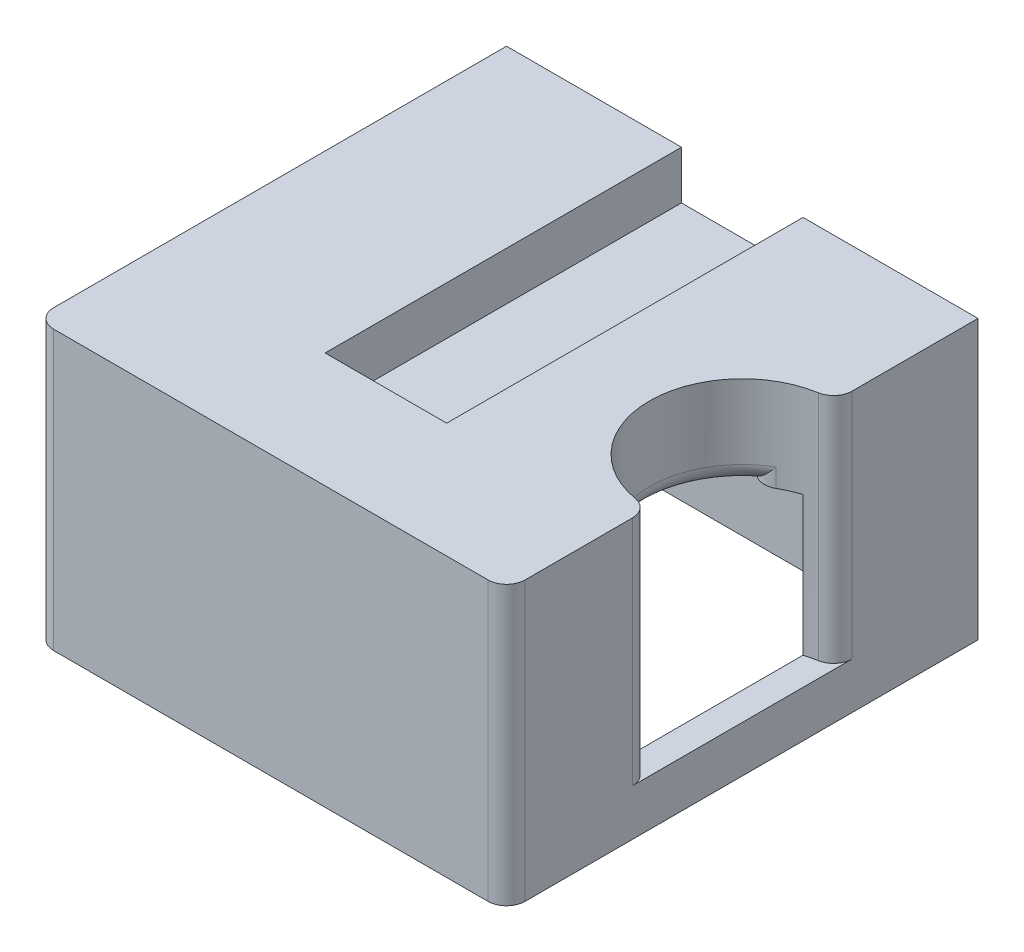
SolidWorks part; units mm, degrees
ref_plane "Front Plane" through (0, 0, 0) normal (0, 0, 1) x (1, 0, 0)
ref_plane "Top Plane" through (0, 0, 0) normal (0, 1, 0) x (1, 0, 0)
ref_plane "Right Plane" through (0, 0, 0) normal (1, 0, 0) x (0, 0, -1)
sketch "Sketch1" plane through (0, 0, 0) normal (0, 1, 0) x (1, 0, 0)
  line L1 (12.7, -12.7) -> (-12.7, -12.7)
  line L2 (12.7, -12.7) -> (12.7, 12.7)
  line L3 (12.7, 12.7) -> (-12.7, 12.7)
  line L4 (-12.7, -12.7) -> (-12.7, 12.7)
  line L5 (12.7, -12.7) -> (-12.7, 12.7) construction
  line L6 (12.7, 12.7) -> (-12.7, -12.7) construction
  line L7 (8.7, -8.7) -> (-8.7, -8.7)
  line L8 (8.7, -8.7) -> (8.7, 8.7)
  line L9 (8.7, 8.7) -> (-8.7, 8.7)
  line L10 (-8.7, -8.7) -> (-8.7, 8.7)
  line L11 (8.7, -8.7) -> (-8.7, 8.7) construction
  line L12 (8.7, 8.7) -> (-8.7, -8.7) construction
  point P0 (0, 0)
  point P6 (0, 0)
  dimension "D1" = 25.4
  dimension "D2" = 25.4
  dimension "D3" = 4
extrude "Boss-Extrude1" add sketch "Sketch1" along normal blind 10
sketch "Sketch2" plane through (0, 0, 0) normal (0, -1, 0) x (-1, 0, 0)
  line L1 (-11.25, 10.75) -> (11.25, 10.75)
  line L2 (-11.25, 10.75) -> (-11.25, -10.75)
  line L3 (-11.25, -10.75) -> (11.25, -10.75)
  line L4 (11.25, 10.75) -> (11.25, -10.75)
  line L5 (-11.25, 10.75) -> (11.25, -10.75) construction
  line L6 (-11.25, -10.75) -> (11.25, 10.75) construction
  point P0 (0, 0)
  dimension "D1" = 22.5
  dimension "D2" = 21.5
hole_wizard "Tap Drill for M2x0.4 Tap1" positions "Sketch3" profile "Sketch4" hole size "M2x0.4" standard "ANSI Metric" end condition through all
sketch "Sketch3" plane through (0, 0, 0) normal (0, -1, 0) x (-1, 0, 0)
  point P0 (11.25, -10.75)
  point P3 (-11.25, -10.75)
  point P6 (-11.25, 10.75)
  point P9 (11.25, 10.75)
sketch "Sketch4" plane through (-11.25, 0, 10.75) normal (1, 0, 0) x (0, 0, -1)
  line L0 (0, 0) -> (0, 10)
  line L1 (0, 10) -> (0.8, 10)
  line L2 (0.8, 10) -> (0.8, 0)
  line L5 (0.8, 0) -> (0, 0)
  line L11 (0, -6.35) -> (0, 107.95) construction
  dimension "Thru Hole Dia." = 1.6
  dimension "Thru Hole Depth" = 10
sketch "Sketch5" plane through (0, 10, 0) normal (0, 1, 0) x (1, 0, 0)
  line L1 (12.7, -12.7) -> (-12.7, -12.7)
  line L2 (12.7, -12.7) -> (12.7, 12.7)
  line L3 (12.7, 12.7) -> (-12.7, 12.7)
  line L4 (-12.7, -12.7) -> (-12.7, 12.7)
extrude "Boss-Extrude2" add sketch "Sketch5" along normal blind 5
sketch "Sketch6" plane through (0, 15, 0) normal (0, 1, 0) x (1, 0, 0)
  line L0 (11.25, 10.75) -> (-11.25, -10.75) construction
  line L1 (-3.275, -12.7) -> (3.275, -12.7)
  line L2 (-3.275, -12.7) -> (-3.275, 12.7)
  line L3 (-3.275, 12.7) -> (3.275, 12.7)
  line L4 (3.275, -12.7) -> (3.275, 12.7)
  line L5 (-3.275, -12.7) -> (3.275, 12.7) construction
  line L6 (-3.275, 12.7) -> (3.275, -12.7) construction
  line L7 (12.7, 12.7) -> (-12.7, 12.7) construction
  line L11 (3.275, -6.5) -> (-3.275, -6.5)
  point P0 (0, 0)
  line M5 (12.7, 12.7) -> (-12.7, 12.7)
  dimension "D1" = 6.55
  dimension "D2" = 19.2
extrude "Cut-Extrude1" cut sketch "Sketch6" against normal blind 2.6 contours L11 L4 L2 M5 region at (0, 15, -3.1)
sketch "Sketch7" plane through (0, 15, 0) normal (0, 1, 0) x (1, 0, 0)
  line L0 (12.7, -12.7) -> (12.7, 12.7) construction
  circle A0 centre (12.7, 0) radius 5
  dimension "D1" = 10
extrude "Cut-Extrude2" cut sketch "Sketch7" against normal blind 12.5
fillet "Fillet1" radius 1 6 edges at (8.7, 2.5, 0) (7.7, 10, 0) (8.7, 6.25, -3) (8.7, 6.25, 3) (12.7, 8.75, -5) (12.7, 8.75, 5)
fillet "Fillet2" radius 1 2 edges at (12.7, 7.5, 12.7) (-12.7, 7.5, 12.7)
sketch "Sketch8" plane through (0, 0, 0) normal (0, -1, 0) x (1, 0, 0)
  line L1 (11.2, -8.8636) -> (-11.2, -8.8636)
  line L2 (11.2, -8.8636) -> (11.2, 9.1364)
  line L3 (11.2, 9.1364) -> (-11.2, 9.1364)
  line L4 (-11.2, -8.8636) -> (-11.2, 9.1364)
  line L5 (11.2, -8.8636) -> (-11.2, 9.1364) construction
  line L6 (11.2, 9.1364) -> (-11.2, -8.8636) construction
  line L7 (-11.7, 12.7) -> (11.7, 12.7) construction
  line L8 (9, -11.2) -> (-9, -11.2)
  line L9 (9, -11.2) -> (9, 11.2)
  line L10 (9, 11.2) -> (-9, 11.2)
  line L11 (-9, -11.2) -> (-9, 11.2)
  line L12 (9, -11.2) -> (-9, 11.2) construction
  line L13 (9, 11.2) -> (-9, -11.2) construction
  line L14 (12.7, 11.7) -> (12.7, -12.7) construction
  line L15 (-12.7, -12.7) -> (-12.7, 11.7) construction
  point P0 (0, 0)
  line M19 (-8.7, -8.7) -> (-8.7, 8.7)
  line M20 (-8.7, 8.7) -> (8.7, 8.7)
  line M21 (8.7, 8.7) -> (8.7, -8.7)
  line M22 (8.7, -8.7) -> (-8.7, -8.7)
  dimension "D1" = 1.5
  dimension "D2" = 1.5
  dimension "D3" = 1.5
  dimension "D4" = 18
  dimension "D5" = 18
extrude "Cut-Extrude3" cut sketch "Sketch8" against normal up to surface (10 mm away) contours L4 L1 L3 M19 | L11 L9 L10 M20 | L2 L3 L1 M21 | L11 L8 L9 M22 | M19 M22 M21 M20 | L11 L1 L9 L3 M22 M19 M20 M21 | L9 L8 L11 L10 region at (10.1, 0, 0.1364) region at (0, 0, -10.0318) region at (0, 0, -8.8382) region at (-10.1, 0, 0.1364) region at (0, 0, 10.1682) region at (0, 0, 0) up to face at (4.1114, 10, 0)
fillet "Fillet3" radius 2 4 edges at (9, 5, -8.8636) (-9, 5, -8.8636) (9, 5, 9.1364) (-9, 5, 9.1364)
